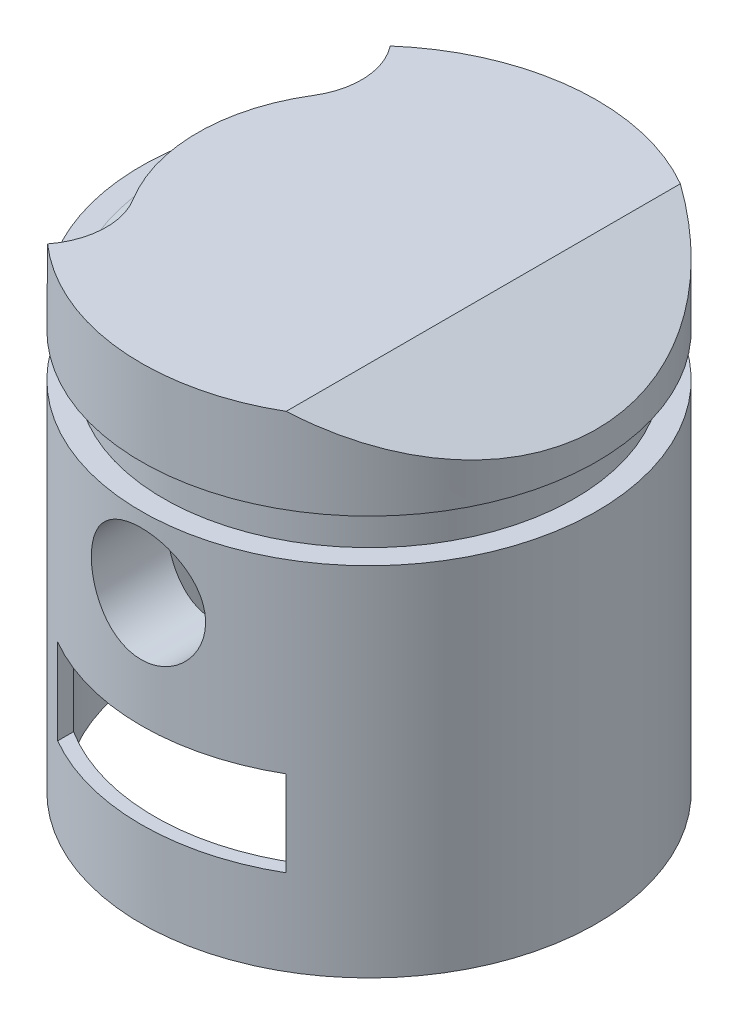
SolidWorks part; units mm, degrees
note: '?' marks a value the reader was unsure of.
ref_plane "Front Plane" through (0, 0, 0) normal (0, 0, 1) x (1, 0, 0)
ref_plane "Top Plane" through (0, 0, 0) normal (0, 1, 0) x (1, 0, 0)
ref_plane "Right Plane" through (0, 0, 0) normal (1, 0, 0) x (0, 0, -1)
sketch "Sketch1" plane through (0, 0, 0) normal (0, 0, 1) x (1, 0, 0)
  line L0 (0, 0) -> (0, 0.0433)
  line L1 (0, 26.9748) -> (12.6619, 26.9748)
  line L2 (12.6619, 26.9748) -> (12.6619, 22.2313)
  line L3 (12.6619, 22.2313) -> (11.43, 22.2313)
  line L4 (11.43, 22.2313) -> (11.43, 19.8438)
  line L5 (11.43, 19.8438) -> (12.6619, 19.8438)
  line L6 (12.6619, 19.8438) -> (12.6619, 0)
  line L8 (0, -1015.1762) -> (0, 0.0433) construction
  line L9 (0, 0) -> (0, 0.0433)
  line L10 (12.6619, 0) -> (11.9062, 0)
  line L11 (11.9062, 0) -> (11.9062, 11.9062)
  line L12 (11.9062, 11.9062) -> (8.7312, 11.9062)
  line L13 (8.7312, 11.9062) -> (8.7312, 23.8125)
  line L14 (8.7312, 23.8125) -> (0, 23.8125)
  line L15 (0, 23.8125) -> (0, 26.9748)
  line L16 (0, 23.8125) -> (0, 1020.6095) construction
  point P15 (0, 0)
  dimension "D1" = 25.3238
  dimension "D2" = 2.3876
  dimension "D3" = 1.2319
  dimension "D4" = 26.9748
  dimension "D5" = 19.8438
  dimension "D6" = 23.8125
  dimension "D7" = 17.4625
  dimension "D8" = 11.9062
  dimension "D9" = 23.8125
revolve "Revolve1" add sketch "Sketch1" angle 360 about L8
sketch "Sketch13" plane through (0, 0, 0) normal (0, 0, 1) x (1, 0, 0)
  line L0 (0, 0) -> (0, 26.9748) construction
  line L1 (12.6619, 26.9748) -> (-12.6619, 26.9748) construction
  circle A0 centre (0, 15.875) radius 3.175
  dimension "D1" = 6.35
  dimension "D2" = 15.875
extrude "Cut-Extrude1" cut sketch "Sketch13" against normal through all both and the other way through all
sketch "Sketch14" plane through (0, 0, 0) normal (0, 0, 1) x (1, 0, 0)
  line L1 (-6.35, 9.525) -> (6.35, 9.525)
  line L2 (-6.35, 9.525) -> (-6.35, 4.7625)
  line L3 (-6.35, 4.7625) -> (6.35, 4.7625)
  line L4 (6.35, 9.525) -> (6.35, 4.7625)
  line L5 (-6.35, 9.525) -> (6.35, 4.7625) construction
  line L6 (-6.35, 4.7625) -> (6.35, 9.525) construction
  point P0 (0, 7.1437)
  point P5 (0, 0)
  dimension "D1" = 12.7
  dimension "D2" = 4.7625
  dimension "D3" = 4.7625
extrude "Cut-Extrude2" cut sketch "Sketch14" against normal through all both and the other way through all
sketch "Sketch15" plane through (0, 0, 0) normal (0, -1, 0) x (1, 0, 0)
  line L0 (-12.6619, 0) -> (12.6619, 0) construction
  line L1 (-3.9688, 12.6619) -> (3.9688, 12.6619) construction
  line L2 (-3.9688, 12.6619) -> (-3.9688, -12.6619) construction
  line L3 (-3.9688, -12.6619) -> (3.9688, -12.6619) construction
  line L4 (3.9688, 12.6619) -> (3.9688, -12.6619) construction
  line L5 (-3.9688, 12.6619) -> (3.9688, -12.6619) construction
  line L6 (-3.9688, -12.6619) -> (3.9688, 12.6619) construction
  line L7 (0, 12.6619) -> (0, -12.6619) construction
  line L8 (3.9688, -12.6619) -> (-3.9688, 12.6619) construction
  line L9 (3.9688, 12.6619) -> (-3.9688, -12.6619) construction
  line L10 (-3.9688, 12.6619) -> (-3.9688, -12.6619) construction
  circle A0 centre (0, 0) radius 12.6619 construction
  arc A1 (7.9375, 8.8744) -> (4.7625, 5.3246) centre (6.35, 7.0995) ccw
  arc A2 (7.9375, -8.8744) -> (7.9375, 8.8744) centre (0, 0) ccw
  arc A3 (7.9375, -8.8744) -> (4.7625, -5.3246) centre (6.35, -7.0995) cw
  circle A4 centre (0, 0) radius 11.9062 construction
  arc A5 (4.7625, 5.3246) -> (4.7625, -5.3246) centre (0, 0) cw
  arc A6 (-4.7625, 5.3246) -> (-4.7625, -5.3246) centre (0, 0) ccw
  arc A7 (-7.9375, -8.8744) -> (-4.7625, -5.3246) centre (-6.35, -7.0995) ccw
  arc A8 (-7.9375, -8.8744) -> (-7.9375, 8.8744) centre (0, 0) cw
  arc A9 (-7.9375, 8.8744) -> (-4.7625, 5.3246) centre (-6.35, 7.0995) cw
  point P0 (0, 0)
  point P15 (7.9375, 8.8744)
  point P26 (7.9375, -8.8744)
  point P30 (-7.9375, -8.8744)
  point P31 (-7.9375, 8.8744)
  dimension "D1" = 7.9375
  dimension "D2" = 4.7625
extrude "Cut-Extrude3" cut sketch "Sketch15" against normal blind 19.05 and the other way through all
ref_axis "Axis1" through (0, 15.875, 7.9245) along (0, 0, 1)?
ref_plane "Plane1" through (0, 0, 12.6619) normal (0, 0, 1) x (1, 0, 0)
sketch "Sketch16" plane through (0, 26.9748, 0) normal (0, 1, 0) x (1, 0, 0)
  line L0 (0, 0) -> (12.5508, 0) construction
  arc A1 (-8.1028, 5.007) -> (-8.3425, 9.525) centre (-11.479, 7.0932) ccw
  arc A2 (-8.1028, -5.007) -> (-8.1028, 5.007) centre (0, 0) cw
  arc A3 (-8.3425, -9.525) -> (-8.3425, 9.525) centre (0, 0) cw
  arc A4 (-8.1028, -5.007) -> (-8.3425, -9.525) centre (-11.479, -7.0932) cw
  circle A5 centre (0, 0) radius 12.6619 construction
  point P3 (-7.3698, 6.0342)
  dimension "D1" = 7.9375
  dimension "D2" = 9.525
  dimension "D3" = 19.05
extrude "Cut-Extrude5" cut sketch "Sketch16" against normal blind 3.175
fillet "Fillet3" radius 1.9844 3 edges at (-7.5158, 23.7998, -7.3035) (-9.525, 23.7998, 0) (-7.5158, 23.7998, 7.3035)
ref_plane "Plane2" through (12.6619, 0, 0) normal (1, 0, 0) x (0, 0, -1)
sketch3d "3DSketch2"
  line L1 (6.35, 26.9748, -10.9545) -> (6.35, 26.9748, 10.9545)
  line L3 (12.6619, 26.9748, 0) -> (12.6619, 0, 0) construction
  line L4 (12.6619, 23.7998, 11.1125) -> (12.6619, 23.7998, -11.1125)
  line L5 (6.35, 26.9748, -10.9545) -> (12.6619, 23.7998, -11.1125)
  line L6 (6.35, 26.9748, 10.9545) -> (12.6619, 23.7998, 11.1125)
  circle A0 centre (0, 0, 0) radius 12.6619 construction
  arc A3 (-8.3425, 26.9748, -9.525) -> (-8.3425, 26.9748, 9.525) centre (0, 26.9748, 0) ccw construction
  point P5 (0, 14.3129, 0)
  point P6 (0, 26.9748, 0)
  point P7 (12.6619, 23.7998, -11.1125)
  point P10 (12.6619, 23.7998, -11.1125)
  point P13 (0, -12.6619, 0)
  point P17 (12.6619, 23.7998, 0)
  dimension "D1" = 6.35
  dimension "D2" = 22.225
  dimension "D3" = 3.175
extrude "Cut-Extrude4" cut sketch "3DSketch2" along direction (0, -1, 0) on the side of the normal through all
